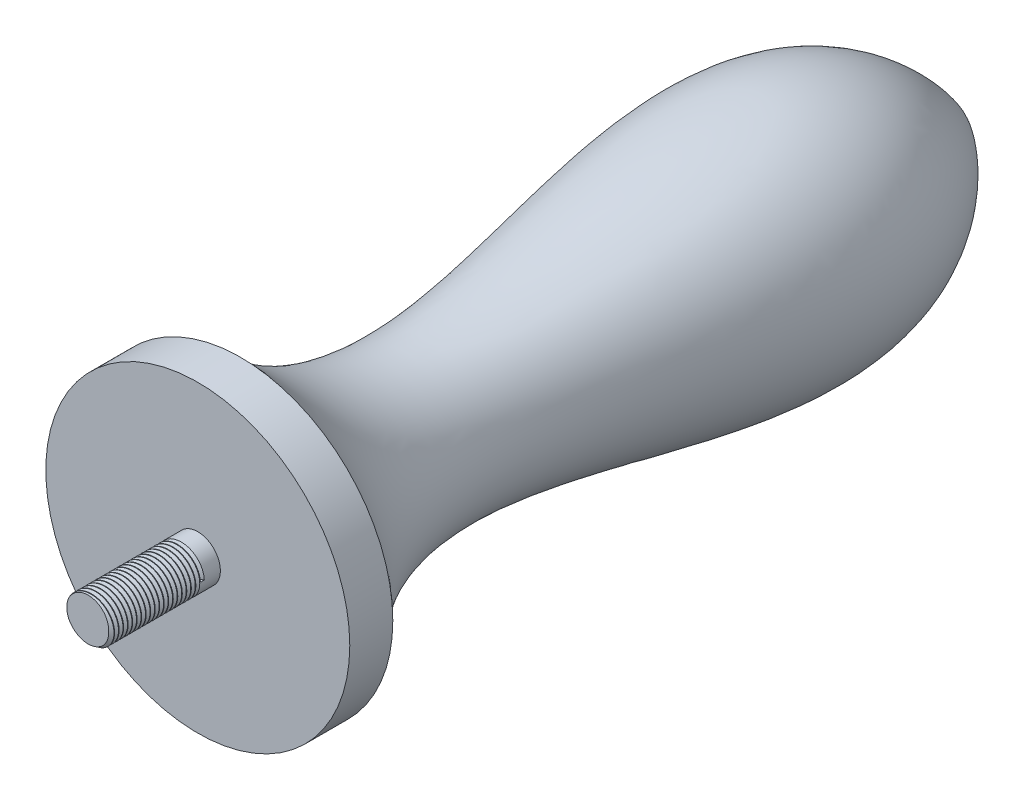
SolidWorks part; units mm, degrees
ref_plane "Front" through (0, 0, 0) normal (0, 0, 1) x (1, 0, 0)
ref_plane "Top" through (0, 0, 0) normal (0, 1, 0) x (1, 0, 0)
ref_plane "Right" through (0, 0, 0) normal (1, 0, 0) x (0, 0, -1)
sketch "Sketch1" plane through (0, 0, 0) normal (0, 0, 1) x (1, 0, 0)
  circle A0 centre (0, 0) radius 2.5
  dimension "D1" = 5
extrude "Boss-Extrude1" add sketch "Sketch1" along normal blind 12
sketch "Sketch2" plane through (0, 0, 0) normal (0, 1, 0) x (1, 0, 0)
  line L0 (0, 0) -> (0, 83.7224) construction
  line L1 (0, 0) -> (-16.8296, 0)
  line L2 (-16.8296, 0) -> (-16.8296, 4.7651)
  line L3 (0, 0) -> (0, 83.7224)
  line L4 (0, 83.7224) -> (-1.7463, 83.7224)
  spline S0 degree 3 poles (-1.7463, 83.7224) (-31.2145, 64.4356) (7.2631, 25.4375) (-16.8296, 4.7651) knots 0 0 0 0 1 1 1 1
  point P3 (-7.7623, 21.8812)
  point P6 (0, 127.3215)
  point P8 (0, 0)
  point P9 (0, 0)
  point P10 (0, 0)
  point P11 (-11.3575, 4.7651)
  point P12 (-4.8762, 12.9325)
  point P13 (0, 0)
  point P14 (0, 0)
  point P15 (0, 0)
  point P16 (0, 111.7458)
  point P17 (0, 83.7224)
sketch "Sketch3" plane through (0, 0, 12) normal (0, 0, 1) x (1, 0, 0)
  circle A0 centre (0, 0) radius 2.5 construction
  circle A1 centre (0, 0) radius 2.5
curve "Helix/Spiral1" pitch 0.5 height 10 radius 2.5 centre (0, 0, 12) axis (0, 0, -1) start towards (1, 0, 0)
ref_plane "Plane1" through (2.5, 0, 12) normal (0, -0.9995, -0.0318) x (-1, 0, 0)
sketch "Sketch4" plane through (2.5, 0, 12) normal (0, -0.9995, -0.0318) x (-1, 0, 0)
  line L1 (0.3757, 0) -> (-0.04, 0.24)
  line L2 (-0.04, 0.24) -> (-0.04, -0.24)
  line L3 (-0.04, -0.24) -> (0.3757, 0)
  circle A0 centre (0.0986, 0) radius 0.1386 construction
  point P1 (0.0986, 0)
  dimension "D1" = 0.48
sweep "Cut-Sweep1" cut profiles "Sketch4" path "Helix/Spiral1" align with end faces yes
revolve "Revolve5" add sketch "Sketch2" angle 360 about L0
